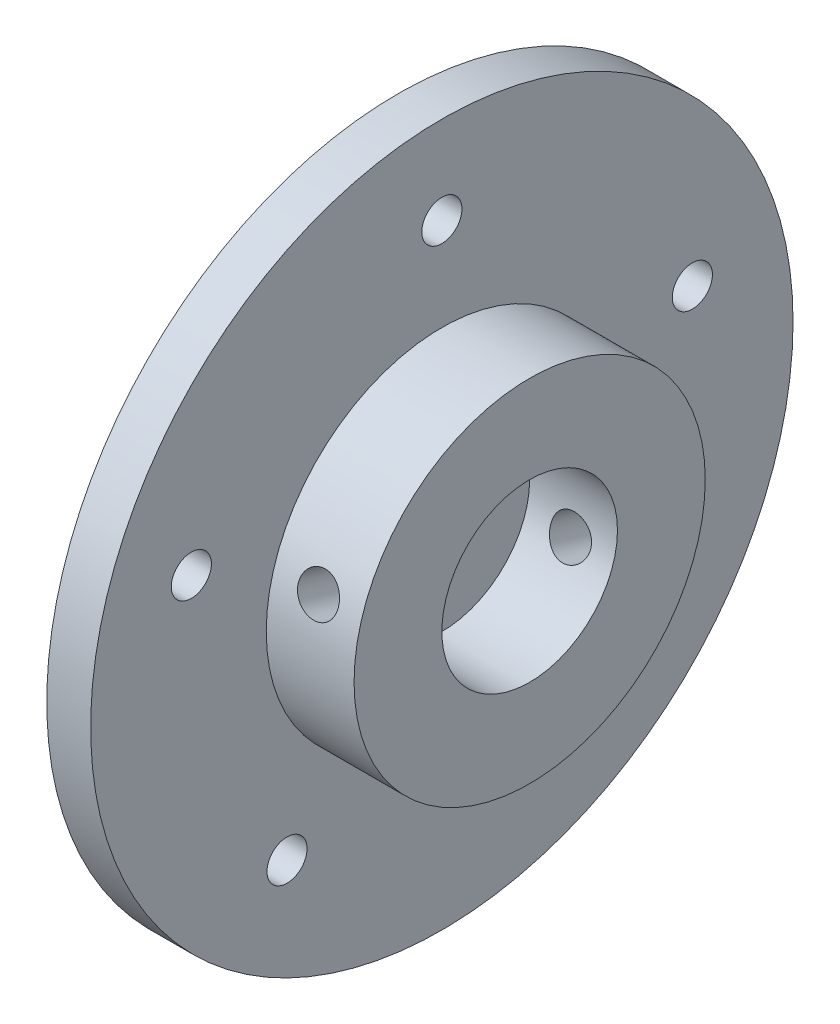
SolidWorks part; units mm, degrees
ref_plane "Front Plane" through (0, 0, 0) normal (0, 0, 1) x (1, 0, 0)
ref_plane "Top Plane" through (0, 0, 0) normal (0, 1, 0) x (1, 0, 0)
ref_plane "Right Plane" through (0, 0, 0) normal (1, 0, 0) x (0, 0, -1)
sketch "Sketch1" plane through (0, 0, 0) normal (1, 0, 0) x (0, 0, -1)
  line L0 (-36.2353, 12.4848) -> (0, 0.7113) construction
  line L1 (0, 0.7113) -> (36.2353, 12.4848) construction
  line L2 (0, 38.8113) -> (0, 0.7113) construction
  line L3 (0, 0.7113) -> (22.3946, -30.1122) construction
  line L4 (-22.3946, -30.1122) -> (0, 0.7113) construction
  circle A0 centre (0, 0.7113) radius 25.4 construction
  circle A1 centre (-36.2353, 12.4848) radius 2.9
  circle A2 centre (-22.3946, -30.1122) radius 2.9
  circle A3 centre (22.3946, -30.1122) radius 2.9
  circle A4 centre (36.2353, 12.4848) radius 2.9
  circle A5 centre (0, 38.8113) radius 2.9
  circle A6 centre (0, 0.7113) radius 50.8
  circle A7 centre (0, 0.7113) radius 38.1 construction
  dimension "D2" = 5.8
  dimension "D3" = 50.8
  dimension "D4" = 101.6
  dimension "D1" = 38.1
  dimension "D5" = 72
  dimension "D6" = 72
  dimension "D7" = 72
  dimension "D8" = 72
  dimension "D9" = 72
extrude "Boss-Extrude1" add sketch "Sketch1" along normal blind 6.35
sketch "Sketch2" plane through (6.35, 0, 0) normal (1, 0, 0) x (0, 0, -1)
  circle A0 centre (0, 0) radius 25.4
  dimension "D1" = 50.8
extrude "Boss-Extrude2" add sketch "Sketch2" along normal blind 12.7
sketch "Sketch3" plane through (19.05, 0, 0) normal (1, 0, 0) x (0, 0, -1)
  circle A0 centre (0, 0) radius 12.7
  dimension "D1" = 25.4
extrude "Cut-Extrude1" cut sketch "Sketch3" against normal blind 12.7
ref_axis "Axis1" through (6.35, 0, 0) along (1, 0, 0)
sketch "Sketch5" plane through (6.35, 0, 0) normal (1, 0, 0) x (0, 0, -1)
  line L0 (22.3946, -30.1122) -> (36.2353, 12.4848) construction
  line L1 (29.3149, -8.8137) -> (0, 0) construction
  line L2 (22.3946, -30.1122) -> (0, 0) construction
  line L3 (0, 0) -> (36.2353, 12.4848) construction
ref_plane "Plane1" through (0, -7.3133, -24.3244) normal (0, -0.2879, -0.9577) x (-1, 0, 0)
sketch "Sketch6" plane through (0, -7.3133, -24.3244) normal (0, -0.2879, -0.9577) x (-1, 0, 0)
  line L0 (0, 0) -> (-19.1518, 0) construction
  line L1 (-19.1518, 0) -> (-12.8211, 0) construction
  circle A0 centre (-12.8211, 0) radius 2.921
  dimension "D1" = 5.842
extrude "Cut-Extrude3" cut sketch "Sketch6" against normal blind 50.8
